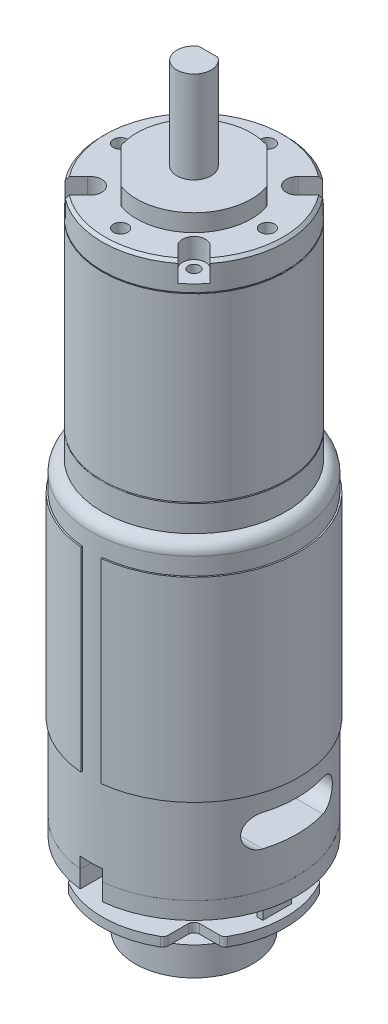
SolidWorks part; units mm, degrees
ref_plane "Alzado" through (0, 0, 0) normal (0, 0, 1) x (1, 0, 0)
ref_plane "Planta" through (0, 0, 0) normal (0, 1, 0) x (1, 0, 0)
ref_plane "Vista lateral" through (0, 0, 0) normal (1, 0, 0) x (0, 0, -1)
sketch "Croquis1" plane through (0, 0, 0) normal (0, 1, 0) x (1, 0, 0)
  circle A0 centre (0, 0) radius 10.25
  dimension "D1" = 20.5
extrude "Saliente-Extruir1" add sketch "Croquis1" along normal blind 5
sketch "Croquis2" plane through (0, 5, 0) normal (0, 1, 0) x (1, 0, 0)
  circle A0 centre (0, 0) radius 2.5
  dimension "D1" = 5
extrude "Saliente-Extruir2" add sketch "Croquis2" along normal blind 3.37
sketch "Croquis3" plane through (0, 8.37, 0) normal (0, 1, 0) x (1, 0, 0)
  line L0 (0, 16) -> (0, 8.5) construction
  line L1 (0, 8.5) -> (8.5, 8.5) construction
  line L2 (8.5, 9.5) -> (8.5, 12.9904)
  line L3 (-8.5, 9.5) -> (-8.5, 12.9904)
  line L4 (9.5, 8.5) -> (12.9904, 8.5)
  line L6 (9.5, -8.5) -> (12.9904, -8.5)
  line L7 (8.5, -9.5) -> (8.5, -12.9904)
  line L9 (-8.5, -9.5) -> (-8.5, -12.9904)
  line L10 (-9.5, -8.5) -> (-12.9904, -8.5)
  line L12 (-9.5, 8.5) -> (-12.9904, 8.5)
  arc A0 (8, 13.8564) -> (-8, 13.8564) centre (0, 0) ccw
  arc A1 (-13.8564, 8) -> (-13.8564, -8) centre (0, 0) ccw
  arc A2 (-8, -13.8564) -> (8, -13.8564) centre (0, 0) ccw
  arc A3 (13.8564, -8) -> (13.8564, 8) centre (0, 0) ccw
  arc A4 (12.9904, 8.5) -> (13.8564, 8) centre (12.9904, 7.5) cw
  arc A5 (-8.5, -12.9904) -> (-8, -13.8564) centre (-7.5, -12.9904) ccw
  arc A6 (8.5, -12.9904) -> (8, -13.8564) centre (7.5, -12.9904) cw
  arc A7 (12.9904, -8.5) -> (13.8564, -8) centre (12.9904, -7.5) ccw
  arc A8 (8.5, 12.9904) -> (8, 13.8564) centre (7.5, 12.9904) ccw
  arc A9 (-8.5, 12.9904) -> (-8, 13.8564) centre (-7.5, 12.9904) cw
  arc A10 (-12.9904, -8.5) -> (-13.8564, -8) centre (-12.9904, -7.5) cw
  arc A11 (-12.9904, 8.5) -> (-13.8564, 8) centre (-12.9904, 7.5) ccw
  arc A12 (9.5, 8.5) -> (8.5, 9.5) centre (9.5, 9.5) cw
  arc A13 (8.5, -9.5) -> (9.5, -8.5) centre (9.5, -9.5) cw
  arc A14 (-9.5, -8.5) -> (-8.5, -9.5) centre (-9.5, -9.5) cw
  arc A15 (-8.5, 9.5) -> (-9.5, 8.5) centre (-9.5, 9.5) cw
  point P1 (0, 0)
  point P24 (0, 0)
  point P43 (-8.5, 8.5)
  dimension "D1" = 32
  dimension "D4" = 1
  dimension "D2" = 17
  dimension "D3" = 7.5
extrude "Saliente-Extruir3" add sketch "Croquis3" along normal blind 1.6 separate body
sketch "Croquis4" plane through (0, 9.97, 0) normal (0, 1, 0) x (1, 0, 0)
  circle A0 centre (0, 0) radius 7.5
  dimension "D1" = 15
extrude "Saliente-Extruir4" add sketch "Croquis4" along normal blind 4.2
sketch "Croquis5" plane through (0, 14.17, 0) normal (0, 1, 0) x (1, 0, 0)
  line L1 (0, 0) -> (8.3207, 0) construction
  line L3 (-1.9463, 17.8945) -> (-1.9463, 13.3945)
  line L4 (-1.9463, 13.3945) -> (1.9518, 13.3945)
  line L5 (1.9518, 13.3945) -> (1.9463, 17.8945)
  line L6 (1.9518, -13.3945) -> (1.9463, -17.8945)
  line L7 (-1.9463, -13.3945) -> (1.9518, -13.3945)
  line L8 (-1.9463, -17.8945) -> (-1.9463, -13.3945)
  line L9 (0, 0) -> (12.3744, 12.3744) construction
  line L16 (0, 0) -> (1.3548, -1.3548) construction
  line L17 (13.0766, 12.3695) -> (12.3744, 11.6673)
  line L18 (12.3744, 11.6673) -> (11.6673, 12.3744)
  line L19 (11.6673, 12.3744) -> (12.3695, 13.0766)
  line L20 (-12.3695, -13.0766) -> (-11.6673, -12.3744)
  line L21 (-11.6673, -12.3744) -> (-12.3744, -11.6673)
  line L22 (-12.3744, -11.6673) -> (-13.0766, -12.3695)
  arc A0 (-1.9463, 17.8945) -> (-13.0766, -12.3695) centre (0, 0) ccw
  arc A1 (1.9463, -17.8945) -> (13.0766, 12.3695) centre (0, 0) ccw
  arc A2 (12.3695, 13.0766) -> (1.9463, 17.8945) centre (0, 0) ccw
  arc A3 (-12.3695, -13.0766) -> (-1.9463, -17.8945) centre (0, 0) ccw
  point P1 (1.9491, 15.6445)
  point P6 (1.9491, -15.6445)
  point P23 (0, 0)
  point P24 (0, 0)
  dimension "D1" = 36
  dimension "D3" = 1
  dimension "D5" = 17
  dimension "D2" = 45
  dimension "D4" = 0.5
  dimension "D6" = 45
extrude "Saliente-Extruir5" add sketch "Croquis5" along normal blind 3 separate body
sketch "Croquis6" plane through (0, 17.17, 0) normal (0, 1, 0) x (1, 0, 0)
  circle A0 centre (0, 0) radius 18
  dimension "D1" = 36
extrude "Saliente-Extruir6" add sketch "Croquis6" along normal blind 54
sketch "Croquis8" plane through (0, 17.17, 0) normal (0, -1, 0) x (1, 0, 0)
  line L0 (1.9518, -13.3945) -> (1.9463, -17.8945) construction
  line L1 (-1.9463, -13.3945) -> (1.9518, -13.3945) construction
  line L2 (-1.9463, -17.8945) -> (-1.9463, -13.3945) construction
  line L3 (1.9518, -13.3945) -> (1.9463, -17.8945)
  line L4 (-1.9463, -13.3945) -> (1.9518, -13.3945)
  line L5 (-1.9463, -17.8945) -> (-1.9463, -13.3945)
  line L6 (-1.9463, 17.8945) -> (-1.9463, 13.3945) construction
  line L7 (-1.9463, 13.3945) -> (1.9518, 13.3945) construction
  line L8 (1.9518, 13.3945) -> (1.9463, 17.8945) construction
  line L9 (-1.9463, 17.8945) -> (-1.9463, 13.3945)
  line L10 (-1.9463, 13.3945) -> (1.9518, 13.3945)
  line L11 (1.9518, 13.3945) -> (1.9463, 17.8945)
  circle A0 centre (0, 0) radius 18 construction
  arc A1 (1.9463, 17.8945) -> (-1.9463, 17.8945) centre (0, 0) ccw
  arc A2 (-1.9463, -17.8945) -> (1.9463, -17.8945) centre (0, 0) ccw
extrude "Cortar-Extruir1" cut sketch "Croquis8" against normal blind 2
fillet "Redondeo1" radius 2 1 edges at (0, 71.17, 18)
sketch "Croquis9" plane through (0, 71.17, 0) normal (0, 1, 0) x (1, 0, 0)
  circle A0 centre (0, 0) radius 16
  dimension "D1" = 32
extrude "Saliente-Extruir7" add sketch "Croquis9" along normal blind 4.73
fillet "Redondeo2" radius 0.2 1 edges at (0, 75.9, 16)
sketch "Croquis10" plane through (0, 75.9, 0) normal (0, 1, 0) x (1, 0, 0)
  circle A0 centre (0, 0) radius 16
  dimension "D1" = 32
extrude "Saliente-Extruir8" add sketch "Croquis10" along normal blind 31.5 separate body
sketch "Croquis11" plane through (0, 107.4, 0) normal (0, 1, 0) x (1, 0, 0)
  circle A0 centre (0, 0) radius 16
  dimension "D1" = 32
extrude "Saliente-Extruir9" add sketch "Croquis11" along normal blind 5 separate body
fillet "Redondeo3" radius 0.2 1 edges at (0, 107.4, 16)
chamfer "Chaflán1" distance 0.5 angle 45 1 edges at (0, 112.4, 16)
sketch "Croquis12" plane through (0, 112.4, 0) normal (0, 1, 0) x (1, 0, 0)
  circle A0 centre (0, 12.8) radius 1.25
  circle A2 centre (0, 0) radius 16 construction
  circle A3 centre (12.8, 0) radius 1.25
  circle A4 centre (0, -12.8) radius 1.25
  circle A5 centre (-12.8, 0) radius 1.25
  point P14 (0, 0)
  dimension "D2" = 2.5
  dimension "D3" = 12.8
  dimension "D1" = 32
  dimension "D4" = 4
extrude "Cortar-Extruir2" cut sketch "Croquis12" against normal blind 5.5
sketch "Croquis13" plane through (0, 112.4, 0) normal (0, 1, 0) x (1, 0, 0)
  line L0 (0, 0) -> (11.3137, 11.3137) construction
  line L1 (0, 0) -> (8.5083, 0) construction
  circle A0 centre (9.051, 9.051) radius 1
  circle A1 centre (0, 0) radius 16 construction
  circle A2 centre (0, 0) radius 15.5
  circle A3 centre (0, 0) radius 15.5 construction
  circle A4 centre (0, 0) radius 16 construction
  circle A5 centre (9.051, -9.051) radius 1
  circle A6 centre (-9.051, -9.051) radius 1
  circle A7 centre (-9.051, 9.051) radius 1
  point P19 (0, 0)
  dimension "D1" = 0
  dimension "D3" = 2
  dimension "D4" = 12.8
  dimension "D2" = 45
  dimension "D5" = 4
extrude "Cortar-Extruir4" cut sketch "Croquis13" against normal blind 8.9
sketch "Croquis14" plane through (0, 112.4, 0) normal (0, 1, 0) x (1, 0, 0)
  line L0 (0, 0) -> (9.051, 9.051) construction
  line L1 (0, 0) -> (7.7061, 0) construction
  line L2 (7.6368, 10.4652) -> (9.8108, 12.6392)
  line L3 (10.6841, 7.8965) -> (12.6213, 9.8337)
  line L4 (10.4652, -7.6368) -> (12.6392, -9.8108)
  line L5 (7.8965, -10.6841) -> (9.8337, -12.6213)
  line L6 (-7.6368, -10.4652) -> (-9.8108, -12.6392)
  line L7 (-10.6841, -7.8965) -> (-12.6213, -9.8337)
  line L8 (-10.4652, 7.6368) -> (-12.6392, 9.8108)
  line L9 (-7.8965, 10.6841) -> (-9.8337, 12.6213)
  circle A0 centre (0, 0) radius 16
  circle A2 centre (9.051, -9.051) radius 1
  circle A3 centre (9.051, -9.051) radius 1
  circle A4 centre (9.051, 9.051) radius 1
  circle A5 centre (9.051, 9.051) radius 1
  circle A6 centre (-9.051, 9.051) radius 1
  circle A7 centre (-9.051, 9.051) radius 1
  circle A8 centre (-9.051, -9.051) radius 1
  circle A9 centre (-9.051, -9.051) radius 1
  arc A10 (7.6368, 10.4652) -> (10.6841, 7.8965) centre (9.051, 9.051) ccw
  circle A11 centre (9.051, 9.051) radius 2 construction
  arc A12 (10.4652, -7.6368) -> (7.8965, -10.6841) centre (9.051, -9.051) ccw
  arc A13 (-7.6368, -10.4652) -> (-10.6841, -7.8965) centre (-9.051, -9.051) ccw
  arc A14 (-10.4652, 7.6368) -> (-7.8965, 10.6841) centre (-9.051, 9.051) ccw
  point P40 (0, 0)
  circle M20 centre (9.051, 9.051) radius 1
  circle M21 centre (9.051, -9.051) radius 1
  circle M22 centre (-9.051, -9.051) radius 1
  circle M23 centre (-9.051, 9.051) radius 1
  circle M28 centre (0, 0) radius 15.5
  dimension "D1" = 32
  dimension "D7" = 4
  dimension "D2" = 0
  dimension "D3" = 0
  dimension "D4" = 0
  dimension "D5" = 0
  dimension "D6" = 1
extrude "Cortar-Extruir5" cut sketch "Croquis14" against normal blind 3.5 contours L8 A14 L9 M28 M23 | L6 A13 L7 M28 M22 | L2 A10 L3 M28 M20 | L4 A12 L5 M28 M21 | L3 A0 L2 M28 | L9 A0 L8 M28 | L7 A0 L6 M28 | L5 A0 L4 M28
sketch "Croquis15" plane through (0, 112.4, 0) normal (0, 1, 0) x (1, 0, 0)
  line L0 (3.4485, 9.2794) -> (9.2794, 3.4485)
  line L1 (-9.2794, -3.4485) -> (-3.4485, -9.2794)
  line L2 (0, 0) -> (4.628, -4.628) construction
  line L3 (0, 0) -> (7.0244, 0) construction
  arc A0 (3.046, 9.5248) -> (-9.5248, -3.046) centre (0, 0) ccw
  arc A1 (-3.046, -9.5248) -> (9.5248, 3.046) centre (0, 0) ccw
  arc A2 (9.2794, 3.4485) -> (9.5248, 3.046) centre (8.5723, 2.7414) cw
  arc A3 (-3.4485, -9.2794) -> (-3.046, -9.5248) centre (-2.7414, -8.5723) ccw
  arc A4 (-9.2794, -3.4485) -> (-9.5248, -3.046) centre (-8.5723, -2.7414) cw
  arc A5 (3.4485, 9.2794) -> (3.046, 9.5248) centre (2.7414, 8.5723) ccw
  point P12 (-3.2818, -9.4462)
  dimension "D1" = 20
  dimension "D5" = 1
  dimension "D2" = 45
  dimension "D3" = 18
  dimension "D4" = 9
extrude "Saliente-Extruir10" add sketch "Croquis15" along normal blind 3
sketch "Croquis16" plane through (0, 115.4, 0) normal (0, 1, 0) x (1, 0, 0)
  circle A0 centre (0, 0) radius 3
  point P7 (0, 0)
  dimension "D1" = 6
extrude "Saliente-Extruir11" add sketch "Croquis16" along normal blind 16
sketch "Croquis17" plane through (0, 131.4, 0) normal (0, 1, 0) x (1, 0, 0)
  line L0 (-1.6583, 2.5) -> (1.6583, 2.5)
  circle A0 centre (0, 0) radius 3 construction
  circle A2 centre (0, 0) radius 3
  arc A3 (1.6583, 2.5) -> (-1.6583, 2.5) centre (0, 0) ccw
  dimension "D1" = 2.5
  dimension "D2" = 0
extrude "Cortar-Extruir6" cut sketch "Croquis17" against normal blind 12
sketch "Croquis18" plane through (0, 0, 0) normal (0, -1, 0) x (1, 0, 0)
  circle A0 centre (0, 0) radius 6
  dimension "D1" = 12
extrude "Cortar-Extruir8" cut sketch "Croquis18" against normal blind 0.25 contours A0
sketch "Croquis19" plane through (0, 0.25, 0) normal (0, -1, 0) x (1, 0, 0)
  circle A0 centre (0, 0) radius 1.5
  dimension "D1" = 3
extrude "Cortar-Extruir9" cut sketch "Croquis19" against normal blind 0.5
sketch "Croquis20" plane through (0, 0, 0) normal (0, -1, 0) x (1, 0, 0)
  circle A0 centre (0, 8) radius 1.5
  circle A1 centre (8, 0) radius 1.5
  circle A2 centre (0, -8) radius 1.5
  circle A3 centre (-8, 0) radius 1.5
  point P12 (0, 0)
  dimension "D1" = 3
  dimension "D2" = 8
  dimension "D3" = 4
extrude "Cortar-Extruir10" cut sketch "Croquis20" against normal blind 0.1
ref_plane "Plano1" through (0, 32.17, 0) normal (0, -1, 0) x (-1, 0, 0)
sketch "Croquis21" plane through (0, 32.17, 0) normal (0, -1, 0) x (-1, 0, 0)
  line L0 (-1.9463, -17.8945) -> (-1.9463, -18.1459)
  line L1 (1.5537, -17.9328) -> (1.5537, -18.1837)
  arc A0 (1.5537, -17.9328) -> (-1.9463, -17.8945) centre (0, 0) ccw
  arc A1 (1.5537, -18.1837) -> (-1.9463, -18.1459) centre (0, 0) ccw
  dimension "D1" = 36
  dimension "D2" = 36.5
  dimension "D3" = 3.5
extrude "Saliente-Extruir12" add sketch "Croquis21" against normal blind 34
sketch "Croquis22" plane through (0, 0, 0) normal (1, 0, 0) x (0, 0, -1)
  line L1 (-5.25, 29) -> (5.25, 29)
  line L3 (-5.25, 23.5) -> (5.25, 23.5)
  line L5 (-5.25, 29) -> (5.25, 23.5) construction
  line L6 (-5.25, 23.5) -> (5.25, 29) construction
  arc A0 (-5.25, 29) -> (-5.25, 23.5) centre (-5.25, 26.25) ccw
  arc A1 (5.25, 23.5) -> (5.25, 29) centre (5.25, 26.25) ccw
  point P0 (0, 26.25)
  point P6 (-8, 26.25)
  point P9 (8, 26.25)
  point P10 (0, 0)
  dimension "D3" = 2.75
  dimension "D1" = 5.5
  dimension "D2" = 23.5
  dimension "D4" = 16
extrude "Cortar-Extruir11" cut sketch "Croquis22" against normal mid plane 44
sketch "Croquis23" plane through (0, 14.17, 0) normal (0, -1, 0) x (1, 0, 0)
  line L0 (0, 0) -> (0, 5.0663) construction
  line L1 (14.5, -2.5) -> (13.5, -2.5)
  line L2 (14.5, -2.5) -> (14.5, 2.5)
  line L3 (14.5, 2.5) -> (13.5, 2.5)
  line L4 (13.5, -2.5) -> (13.5, 2.5)
  line L5 (14.5, -2.5) -> (13.5, 2.5) construction
  line L6 (14.5, 2.5) -> (13.5, -2.5) construction
  line L7 (-14.5, -2.5) -> (-13.5, -2.5)
  line L8 (-14.5, -2.5) -> (-14.5, 2.5)
  line L9 (-13.5, -2.5) -> (-13.5, 2.5)
  line L10 (-14.5, 2.5) -> (-13.5, 2.5)
  point P0 (14, 0)
  dimension "D1" = 1
  dimension "D2" = 5
  dimension "D3" = 13.5
extrude "Saliente-Extruir13" add sketch "Croquis23" along normal blind 7
fillet "Redondeo4" radius 0.5 4 edges at (14, 7.17, -2.5) (14, 7.17, 2.5) (-14, 7.17, 2.5) (-14, 7.17, -2.5)
